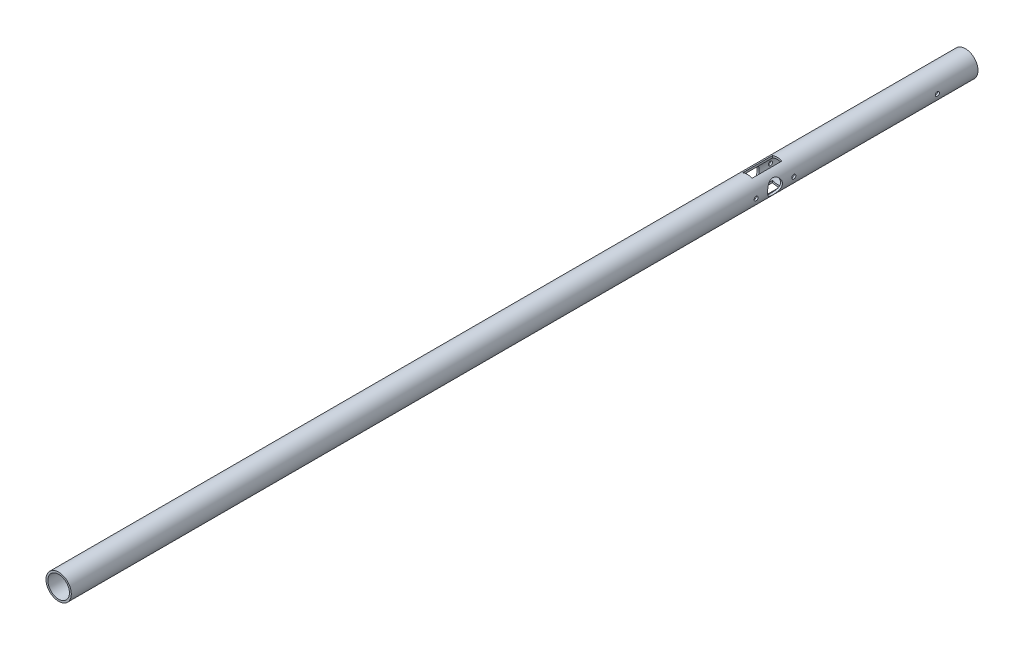
SolidWorks part; units mm, degrees
material "6061-T4 (SS)"
ref_plane "Front" through (0, 0, 0) normal (0, 0, 1) x (1, 0, 0)
ref_plane "Top" through (0, 0, 0) normal (0, 1, 0) x (1, 0, 0)
ref_plane "Right" through (0, 0, 0) normal (1, 0, 0) x (0, 0, -1)
sketch "Sketch1" plane through (0, 0, 0) normal (0, 0, 1) x (1, 0, 0)
  circle A0 centre (0, 0) radius 9.36
  circle A1 centre (0, 0) radius 7.99
  dimension "D1" = 18.72
  dimension "D2" = 15.98
extrude "Extrude1" add sketch "Sketch1" along normal blind 670
sketch "Sketch2" plane through (0, 0, 0) normal (1, 0, 0) x (0, 0, -1)
  line L0 (-30, -47.5362) -> (-30, 39.1475) construction
  line L1 (0, -9.36) -> (0, 9.36) construction
  line L2 (-150, -93.5027) -> (-150, 51.4365) construction
  line L3 (-670, 9.36) -> (-670, -9.36) construction
  circle A0 centre (-30, 0) radius 1.5
  circle A1 centre (-150, 0) radius 5.5
  circle A2 centre (-136.0625, 0) radius 1.5
  circle A3 centre (-163.9375, 0) radius 1.5
  point P10 (-163.9375, 0)
  point P11 (-136.0625, 0)
  point P16 (-670, 0)
  dimension "D2" = 150
  dimension "D3" = 13.9375
  dimension "D5" = 506.0625
  dimension "D1" = 30
  dimension "D4" = 13.9375
extrude "Extrude2" cut sketch "Sketch2" against normal through all and the other way through all
sketch "Sketch3" plane through (0, 0, 0) normal (0, 1, 0) x (1, 0, 0)
  line L0 (-54.8402, -150) -> (72.4613, -150) construction
  line L1 (7.99, 0) -> (-7.99, 0) construction
  line L2 (-44.3384, -139) -> (38.4408, -139) construction
  line L3 (-76.6388, -161) -> (67.6466, -161) construction
  line L4 (3.5, -160.8387) -> (3.5, -87.3966) construction
  line L5 (0, -179.9469) -> (0, -88.7091) construction
  line L6 (-3.5, -169.4108) -> (-3.5, -98.3485) construction
  line L8 (-3.5, -139) -> (3.5, -139)
  line L9 (-3.5, -139) -> (-3.5, -161)
  line L10 (-3.5, -161) -> (3.5, -161)
  line L11 (3.5, -139) -> (3.5, -161)
  dimension "D1" = 150
  dimension "D2" = 11
  dimension "D3" = 22
  dimension "D4" = 3.5
  dimension "D5" = 7
extrude "Extrude3" cut sketch "Sketch3" against normal blind 25 and the other way blind 25
